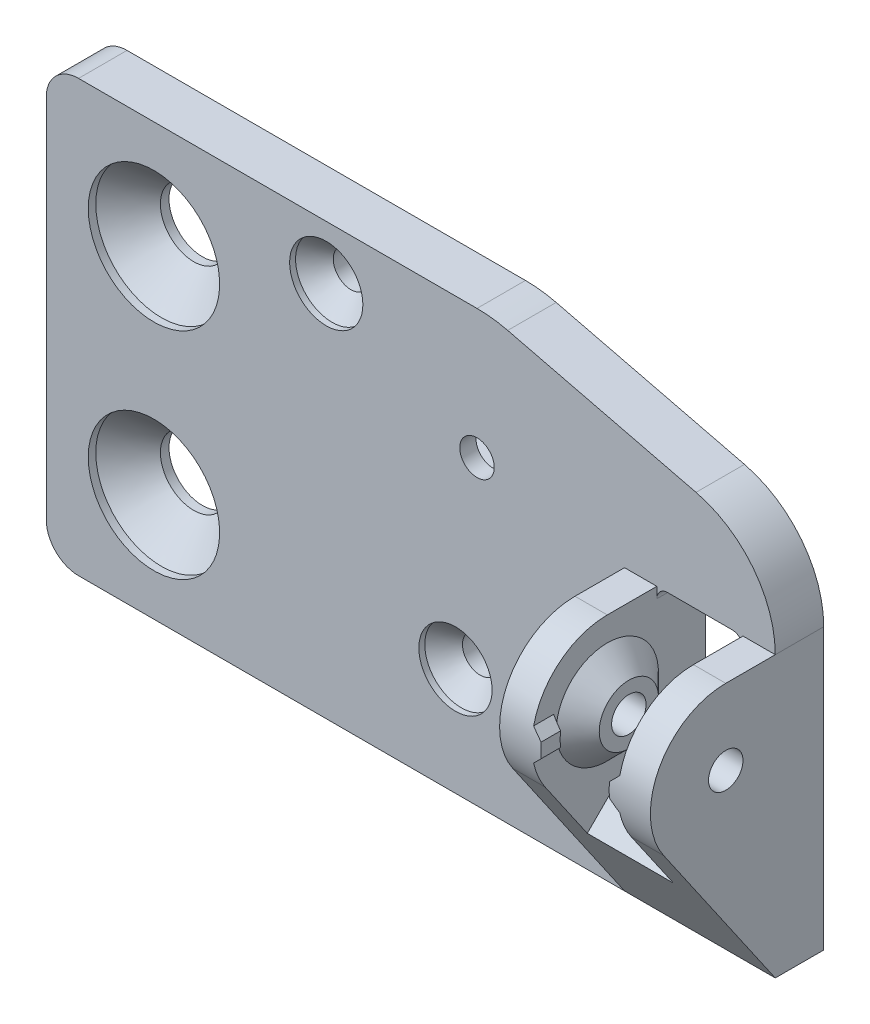
SolidWorks part; units mm, degrees
material "Custom Plastic"
ref_plane "Front Plane" through (0, 0, 0) normal (0, 0, 1) x (1, 0, 0)
ref_plane "Top Plane" through (0, 0, 0) normal (0, 1, 0) x (1, 0, 0)
ref_plane "Right Plane" through (0, 0, 0) normal (1, 0, 0) x (0, 0, -1)
sketch "Sketch1" plane through (0, 0, 0) normal (0, 0, 1) x (1, 0, 0)
  line L0 (-10, -20) -> (-10, 0) construction
  line L1 (-10, -20) -> (10, -20) construction
  line L2 (-10, 0) -> (10, 0) construction
  line L3 (10, -20) -> (10, 0) construction
  line L4 (-10, -20) -> (10, 0) construction
  line L5 (-10, 0) -> (10, -20) construction
  line L6 (-10, 0) -> (-10, 20) construction
  line L7 (-10, 17) -> (-10, -17)
  line L8 (-10, 20) -> (10, 20) construction
  line L9 (10, 0) -> (10, 20) construction
  line L10 (-10, 0) -> (10, 20) construction
  line L11 (-10, 20) -> (10, 0) construction
  line L12 (-7, 20) -> (10, 20)
  line L13 (57.7, 20) -> (57.7, -20)
  line L15 (10, 20) -> (57.7, 20)
  line L18 (57.7, -20) -> (-7, -20)
  circle A0 centre (0, 10) radius 3.1
  circle A1 centre (0, -10) radius 3.1
  arc A2 (-7, 20) -> (-10, 17) centre (-7, 17) ccw
  arc A3 (-10, -17) -> (-7, -20) centre (-7, -17) ccw
  circle A4 centre (30, 8) radius 1.6
  point P0 (0, 10)
  point P1 (0, -10)
  dimension "D2" = 6.2
  dimension "D6" = 3
  dimension "D4" = 3.2
  dimension "D1" = 20
  dimension "D3" = 57.7
  dimension "D5" = 20
  dimension "D7" = 8
extrude "Boss-Extrude1" add sketch "Sketch1" along normal blind 4.5
sketch "Sketch2" plane through (0, -20, 0) normal (0, -1, 0) x (1, 0, 0)
  line L0 (10, 0) -> (10, -16)
  line L2 (10, -16) -> (19, -16)
  line L3 (19, -16) -> (57.7, 0)
  line L4 (57.7, 0) -> (10, 0)
  dimension "D1" = 16
  dimension "D2" = 10
  dimension "D3" = 9
extrude "Boss-Extrude2" add sketch "Sketch2" against normal blind 15
sketch "Sketch3" plane through (57.7, 0, 0) normal (1, 0, 0) x (0, 0, -1)
  line L0 (-9.1, 6) -> (-4.5, 6)
  line L1 (-4.5, -20) -> (-14.8625, -4.9741)
  line L2 (-4.5, 6) -> (-4.5, -20)
  line L3 (-4.5, -20) -> (-4.5, 20) construction
  arc A0 (-9.1, 6) -> (-14.8625, -4.9741) centre (-9.1, -1) ccw
  dimension "D1" = 7
  dimension "D2" = 1
  dimension "D3" = 4.6
extrude "Boss-Extrude3" add sketch "Sketch3" against normal blind 14
sketch "Sketch4" plane through (0, -5, 0) normal (0, 1, 0) x (1, 0, 0)
  line L1 (10, 0) -> (57.7, 0)
  line L2 (10, 0) -> (10, 5.1)
  line L3 (10, 5.1) -> (19, 5.1)
  line L4 (57.7, 0) -> (57.7, 16)
  line L5 (19, 16) -> (19, 5.1)
  line L6 (19, 16) -> (57.7, 16)
  line L7 (57.7, 0) -> (10, 0) construction
  line L8 (10, 0) -> (10, 16) construction
  dimension "D1" = 5.1
extrude "Cut-Extrude1" cut sketch "Sketch4" against normal offset from surface (11 mm away) 4 contours L6 L4 L1 L2 L3 L5 up to face at (17.9063, -20, -1.3125)
sketch "Sketch5" plane through (57.7, 0, 0) normal (1, 0, 0) x (0, 0, -1)
  circle A0 centre (-9.1, -1) radius 1.6
  dimension "D1" = 3.2
extrude "Cut-Extrude2" cut sketch "Sketch5" against normal through all
sketch "Sketch6" plane through (57.7, 0, 0) normal (1, 0, 0) x (0, 0, -1)
  line L0 (-5.2109, -4.8891) -> (-19.2142, -18.8924)
  line L1 (-19.2142, -18.8924) -> (-19.2142, 16.8924)
  line L2 (-19.2142, 16.8924) -> (-5.2109, 2.8891)
  arc A0 (-5.2109, -4.8891) -> (-5.2109, 2.8891) centre (-9.1, -1) ccw
  dimension "D1" = 5.5
extrude "Cut-Extrude3" cut sketch "Sketch6" against normal blind 8 from offset 3 offset against normal yes
fillet "Fillet1" radius 5 1 edges at (14.5, -5, -16)
sketch "Sketch7" plane through (19, 0, 0) normal (1, 0, 0) x (0, 0, -1)
  line L2 (16, -20) -> (0, -20) construction
  line L3 (16, -16) -> (16, -20) construction
  circle A0 centre (11, -10) radius 2.1
  dimension "D1" = 4.2
  dimension "D2" = 10
  dimension "D3" = 5
extrude "Cut-Extrude4" cut sketch "Sketch7" against normal through all
sketch "Sketch8" plane through (19, 0, 0) normal (1, 0, 0) x (0, 0, -1)
  circle A0 centre (11, -10) radius 4.1
  dimension "D1" = 8.2
extrude "Cut-Extrude5" cut sketch "Sketch8" against normal offset from surface (1.5 mm away) 7.5 up to face at (10, -12.1, -11)
chamfer "Chamfer1" distance 2 angle 45 1 edges at (17.5, -12.1, -11)
ref_axis "Axis1" through (54.7, -1, 9.1) along (1, 0, 0)
sketch "Sketch9" plane through (0, 0, 0) normal (0, 0, 1) x (1, 0, 0)
  line L0 (46.7, -4.8891) -> (46.7, 2.8891) construction
  line L1 (46.7, 6) -> (54.7, 6)
  line L2 (46.7, 6) -> (46.7, 3.5)
  line L3 (46.7, 3.5) -> (54.7, 3.5) construction
  line L4 (54.7, 6) -> (54.7, 3.5)
  line L5 (54.7, 2.8891) -> (54.7, -4.8891) construction
  line L6 (54.7, 2.8891) -> (54.7, 6) construction
  line L7 (46.7, -5.5) -> (54.7, -5.5) construction
  line L8 (46.7, -5.5) -> (46.7, -8)
  line L9 (46.7, -8) -> (54.7, -8)
  line L10 (54.7, -5.5) -> (54.7, -8)
  line L11 (54.7, 3.5) -> (54.7, -5.5)
  line L12 (54.7, -1) -> (57.7, -1) construction
  line L13 (46.7, 3.5) -> (46.7, -5.5)
  point P14 (54.7, -1)
  dimension "D1" = 2.5
  dimension "D2" = 9
extrude "Cut-Extrude6" cut sketch "Sketch9" along normal through all
sketch "Sketch10" plane through (0, 0, 0) normal (0, 0, -1) x (-1, 0, 0)
  line L1 (-57.7, 6) -> (-57.7, 20)
  line L2 (-57.7, 20) -> (-30, 20)
  line L3 (-50.34, 15.3777) -> (-32.8517, 19.6562)
  arc A0 (-30, 20) -> (-32.8517, 19.6562) centre (-30, 8) ccw
  arc A1 (-50.34, 15.3777) -> (-57.7, 6) centre (-48.0457, 6) ccw
extrude "Cut-Extrude7" cut sketch "Sketch10" against normal through all
sketch "Sketch11" plane through (0, 0, 0) normal (0, 0, -1) x (-1, 0, 0)
  line L1 (-30.75, -8.4123) -> (-30.75, -11.5877) construction
  line L2 (-30.75, -11.5877) -> (-28, -13.1754) construction
  line L3 (-28, -13.1754) -> (-25.25, -11.5877) construction
  line L4 (-25.25, -11.5877) -> (-25.25, -8.4123) construction
  line L5 (-25.25, -8.4123) -> (-28, -6.8246) construction
  line L6 (-28, -6.8246) -> (-30.75, -8.4123) construction
  line L7 (-13.25, 13.4123) -> (-13.25, 16.5877) construction
  line L8 (-13.25, 16.5877) -> (-16, 18.1754) construction
  line L9 (-16, 18.1754) -> (-18.75, 16.5877) construction
  line L10 (-18.75, 16.5877) -> (-18.75, 13.4123) construction
  line L11 (-18.75, 13.4123) -> (-16, 11.8246) construction
  line L12 (-16, 11.8246) -> (-13.25, 13.4123) construction
  circle A0 centre (-16, 15) radius 1.65
  circle A1 centre (-28, -10) radius 1.65
  circle A2 centre (-28, -10) radius 2.75 construction
  circle A3 centre (-16, 15) radius 2.75 construction
  circle A4 centre (-30, 8) radius 1.6 construction
  point P20 (-30, 8)
  dimension "D1" = 3.3
  dimension "D2" = 5.5
  dimension "D5" = 2
  dimension "D6" = 10
  dimension "D3" = 14
  dimension "D4" = 15
extrude "Cut-Extrude9" cut sketch "Sketch11" against normal through all
sketch "Sketch13" plane through (46.7, 0, 0) normal (1, 0, 0) x (0, 0, -1)
  circle A0 centre (-9.1, -1) radius 2.75
  circle A1 centre (-9.1, -1) radius 1.6
  circle A4 centre (-9.1, -1) radius 1.6 construction
  point P9 (4.6036, -2.5)
  point P11 (10.6036, -2.5)
  point P12 (4.6036, 0.5)
  point P13 (10.6036, 0.5)
  dimension "D1" = 5.5
extrude "Boss-Extrude4" add sketch "Sketch13" along normal blind 2
sketch "Sketch15" plane through (46.7, 0, 0) normal (1, 0, 0) x (0, 0, -1)
  line L0 (-14.079, 0.5) -> (-15.9374, 0.5)
  line L2 (-14.079, -2.5) -> (-15.9374, -2.5)
  arc A1 (-15.9374, 0.5) -> (-15.9374, -2.5) centre (-9.1, -1) ccw
  arc A2 (-9.1, 6) -> (-14.8625, -4.9741) centre (-9.1, -1) ccw construction
  arc A3 (-9.1, 6) -> (-14.8625, -4.9741) centre (-9.1, -1) ccw construction
  arc A4 (-14.079, 0.5) -> (-14.079, -2.5) centre (-9.1, -1) ccw
  dimension "D4" = 5.2
  dimension "D3" = 3
extrude "Boss-Extrude5" add sketch "Sketch15" along normal blind 0.825
ref_plane "Plane1" through (50.7, 0, 0) normal (1, 0, 0) x (0, 0, -1)
mirror "Mirror1" about plane through (50.7, 0, 0) normal (1, 0, 0) of "Boss-Extrude5", "Boss-Extrude4"
chamfer "Chamfer3" distance 2 angle 45 2 edges at (54.7, 1.75, 9.1) (46.7, 1.75, 9.1)
sketch "Sketch14" plane through (0, 0, 4.5) normal (0, 0, -1) x (-1, 0, 0)
  circle A0 centre (0, -10) radius 6.1
  circle A1 centre (0, 10) radius 6.1
  dimension "D1" = 12.2
extrude "Cut-Extrude10" cut sketch "Sketch14" along normal blind 0.7
chamfer "Chamfer4" distance 3 angle 45 2 edges at (-3.1, -10, 3.8) (-3.1, 10, 3.8)
chamfer "Chamfer5" distance 0.83 angle 45 4 edges at (53.875, -2.5, 15.0082) (53.875, 0.5, 15.0082) (47.525, -2.5, 15.0082) (47.525, 0.5, 15.0082)
sketch "Sketch16" plane through (0, 0, 4.5) normal (0, 0, -1) x (-1, 0, 0)
  circle A0 centre (-28, -10) radius 3.4
  circle A1 centre (-16, 15) radius 3.4
  dimension "D1" = 6.8
extrude "Cut-Extrude11" cut sketch "Sketch16" along normal blind 0.5
chamfer "Chamfer6" distance 1.8 angle 45 2 edges at (26.35, -10, 4) (14.35, 15, 4)
sketch "Sketch17" plane through (10, 0, 0) normal (-1, 0, 0) x (0, 0, 1)
  line L0 (-11, -10) -> (-9.5151, -8.5151)
  line L1 (-9.5151, -8.5151) -> (-10.5502, -7.48)
  line L2 (-10.5502, -7.48) -> (-11.4498, -7.48)
  line L3 (-11.4498, -7.48) -> (-12.4849, -8.5151)
  line L4 (-12.4849, -8.5151) -> (-11, -10)
  circle A0 centre (-11, -10) radius 2.1 construction
  point P0 (-11, -7.9)
  dimension "D1" = 0.42
extrude "Cut-Extrude12" cut sketch "Sketch17" against normal through all
sketch "Sketch18" plane through (0, 0, 0) normal (0, 0, -1) x (-1, 0, 0)
  circle A0 centre (-30, 8) radius 6.25
  dimension "D1" = 12.5
extrude "Cut-Extrude13" cut sketch "Sketch18" against normal blind 3
fillet "Fillet2" radius 1 2 edges at (46.7, 6, 2.25) (54.7, 6, 2.25)
equation "\"y-cross-rib-thickness\"=4"
equation "\"y-rib-thickness\"=6"
equation "\"bed-plate-thickness\"=3"
equation "\"x-plate-thickness\"=5"
equation "\"rod-diameter\"=12"
equation "\"t-nut-hole-diameter\"=3"
equation "\"y-plate-thickness\"=5"
equation "\"D1@Sketch4\"=\"y-plate-thickness\"+.1"
equation "\"D1@Boss-Extrude5\"=(8-6.35)/2"
